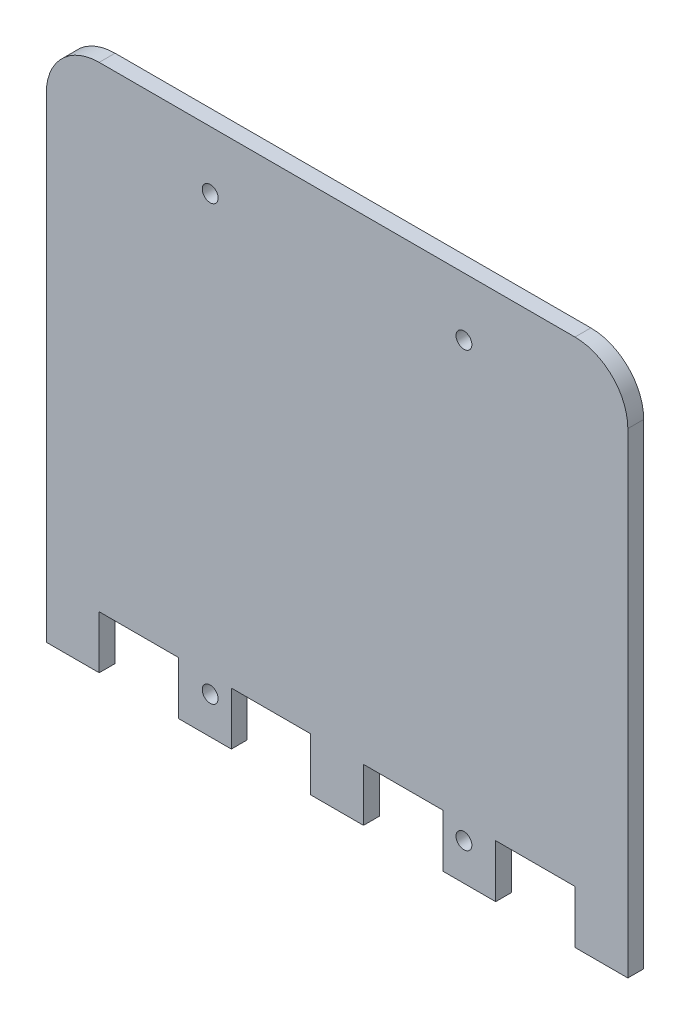
SolidWorks part; units mm, degrees
ref_plane "Спереди" through (0, 0, 0) normal (0, 0, 1) x (1, 0, 0)
ref_plane "Сверху" through (0, 0, 0) normal (0, 1, 0) x (1, 0, 0)
ref_plane "Справа" through (0, 0, 0) normal (1, 0, 0) x (0, 0, -1)
sketch "Эскиз1" plane through (0, 0, 0) normal (0, 0, 1) x (1, 0, 0)
  line L0 (-20, -45) -> (-20, -55)
  line L1 (45, -45) -> (30, -45)
  line L2 (55, -45) -> (55, 35)
  line L3 (45, 45) -> (-45, 45)
  line L4 (-55, -45) -> (-55, 35)
  line L5 (55, -45) -> (-55, 45) construction
  line L6 (55, 45) -> (-55, -45) construction
  line L12 (-55, -45) -> (-55, -55)
  line L13 (-55, -55) -> (-45, -55)
  line L14 (-45, -45) -> (-45, -55)
  line L15 (-30, -55) -> (-20, -55)
  line L16 (-30, -45) -> (-30, -55)
  line L17 (5, -45) -> (5, -55)
  line L18 (-5, -55) -> (5, -55)
  line L19 (-5, -45) -> (-5, -55)
  line L20 (30, -45) -> (30, -55)
  line L21 (20, -55) -> (30, -55)
  line L22 (20, -45) -> (20, -55)
  line L23 (55, -45) -> (55, -55)
  line L24 (45, -55) -> (55, -55)
  line L25 (45, -45) -> (45, -55)
  line L26 (-30, -45) -> (-45, -45)
  line L27 (-5, -45) -> (-20, -45)
  line L28 (20, -45) -> (5, -45)
  arc A0 (55, 35) -> (45, 45) centre (45, 35) ccw
  arc A1 (-45, 45) -> (-55, 35) centre (-45, 35) ccw
  point P0 (0, 0)
  dimension "D3" = 10
  dimension "D1" = 110
  dimension "D2" = 90
  dimension "D4" = 10
  dimension "D5" = 10
  dimension "D6" = 5
extrude "Бобышка-Вытянуть2" add sketch "Эскиз1" along normal mid plane 3
sketch "Эскиз2" plane through (0, 0, 1.5) normal (0, 0, 1) x (1, 0, 0)
  line L5 (45, 45) -> (-45, 45) construction
  line L6 (50, -54) -> (-30, -54) construction
  line L7 (50, -54) -> (50, 40) construction
  line L8 (50, 40) -> (-30, 40) construction
  line L9 (-30, -54) -> (-30, 40) construction
  line L10 (50, -54) -> (-30, 40) construction
  line L11 (50, 40) -> (-30, -54) construction
  line L12 (55, -55) -> (55, 35) construction
  point P0 (10, -7)
  dimension "D1" = 5
  dimension "D2" = 80
  dimension "D3" = 5
  dimension "D4" = 94
sketch "Эскиз3" plane through (0, 0, 1.5) normal (0, 0, 1) x (1, 0, 0)
  line L1 (50, 40) -> (-30, 40) construction
  line L3 (-30, -54) -> (-30, 40) construction
  line L4 (0, 0) -> (0, 22.2229) construction
  line L6 (10, -7) -> (-8.2285, -7) construction
  circle A0 centre (-24, 34) radius 1.5
  circle A1 centre (24, 34) radius 1.5
  circle A2 centre (24, -48) radius 1.5
  circle A3 centre (-24, -48) radius 1.5
  dimension "D1" = 6
  dimension "D2" = 6
extrude "Вырез-Вытянуть1" cut sketch "Эскиз3" against normal up to surface (3 mm away) up to face at (0, -33.9026, -1.5)
